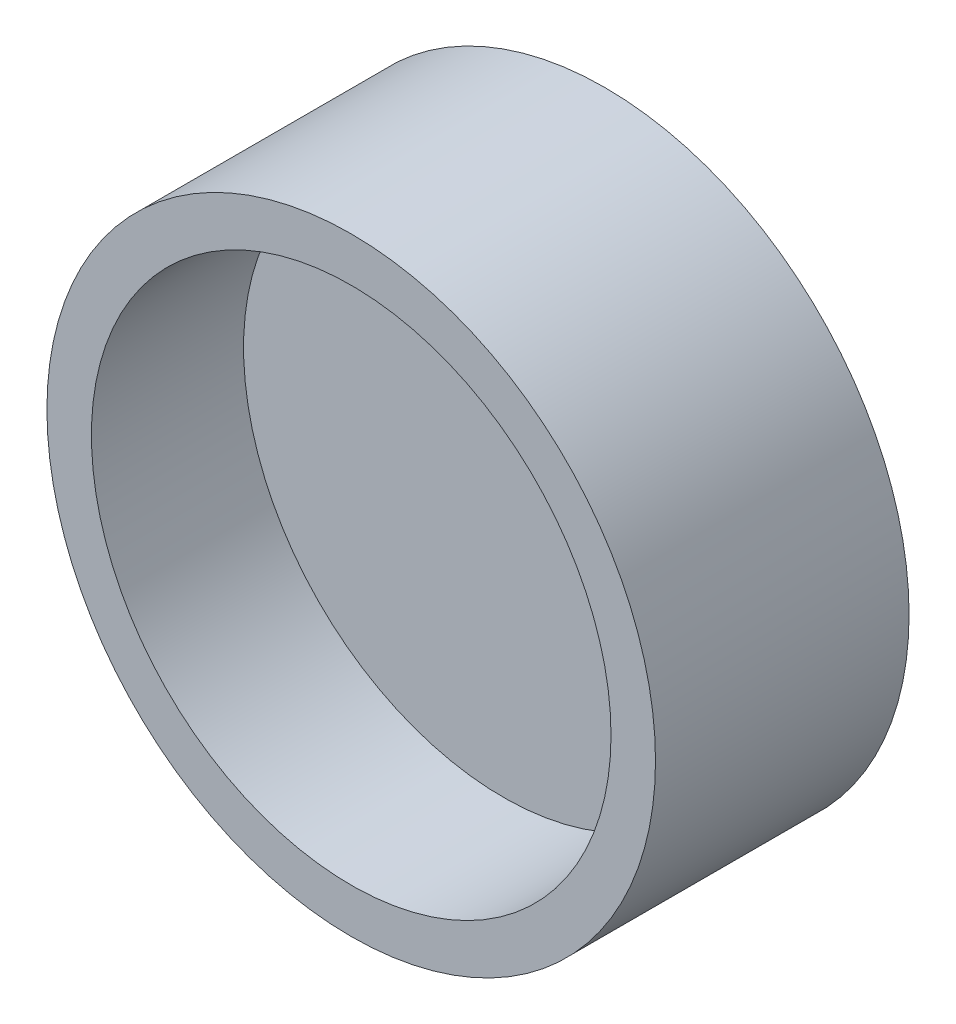
SolidWorks part; units mm, degrees
ref_plane "Front Plane" through (0, 0, 0) normal (0, 0, 1) x (1, 0, 0)
ref_plane "Top Plane" through (0, 0, 0) normal (0, 1, 0) x (1, 0, 0)
ref_plane "Right Plane" through (0, 0, 0) normal (1, 0, 0) x (0, 0, -1)
sketch "Sketch1" plane through (0, 0, 0) normal (0, 0, 1) x (1, 0, 0)
  circle A0 centre (0, 0) radius 30
  circle A1 centre (0, 0) radius 25.6139
  dimension "D1" = 60
extrude "Boss-Extrude1" add sketch "Sketch1" along normal blind 10 contours A1
extrude "Boss-Extrude2" add sketch "Sketch1<3>" along normal blind 25
sketch "Sketch1<3>" plane through (0, 0, 0) normal (0, 0, 1) x (1, 0, 0) same geometry as "Sketch1"
